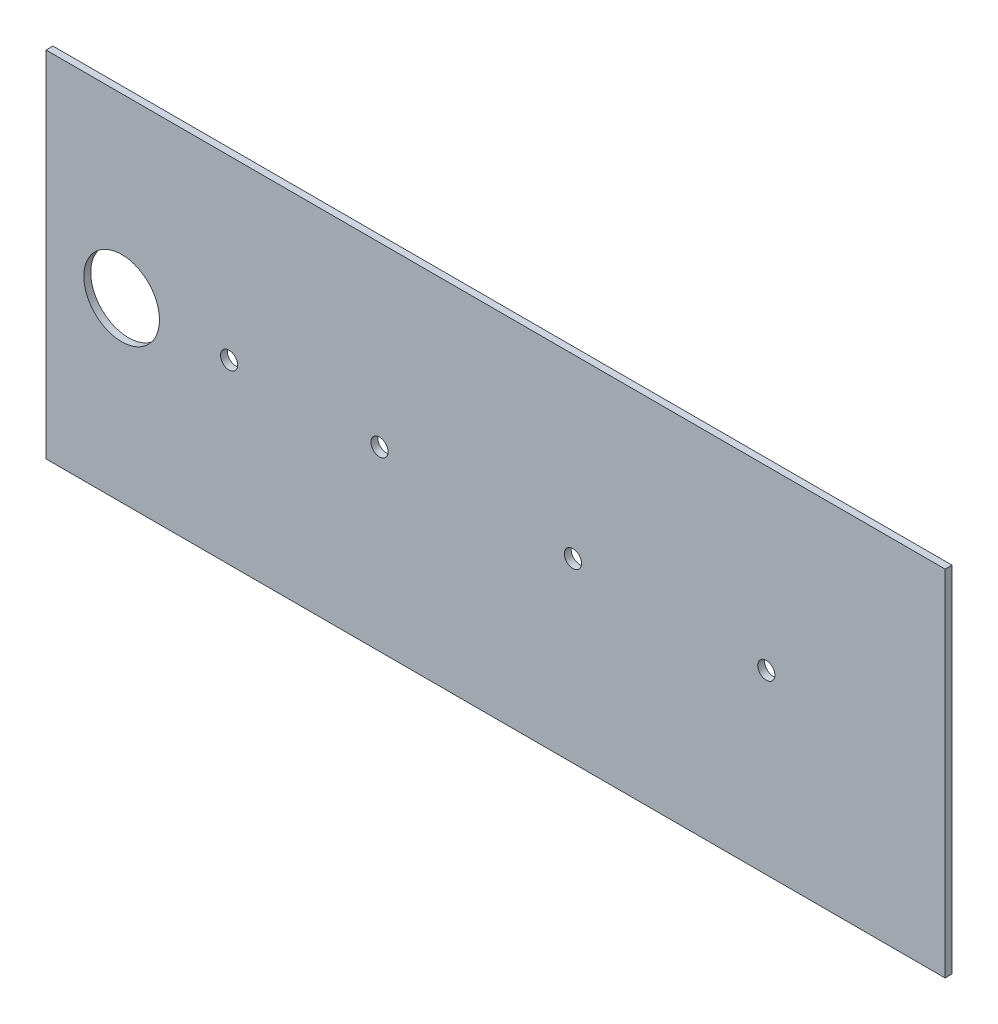
SolidWorks part; units mm, degrees
material "Сталь ШХ15 ГОСТ 801-78"
ref_plane "Plane1" through (0, 0, 0) normal (0, 0, 1) x (1, 0, 0)
ref_plane "Plane2" through (0, 0, 0) normal (0, 1, 0) x (1, 0, 0)
ref_plane "Plane3" through (0, 0, 0) normal (1, 0, 0) x (0, 0, -1)
sketch "Эскиз1" plane through (0, 0, 0) normal (0, 0, 1) x (1, 0, 0)
  line L0 (0, 51.5) -> (261.5, 51.5) construction
  line L1 (0, 0) -> (261.5, 0)
  line L2 (0, 0) -> (0, 103)
  line L3 (0, 103) -> (261.5, 103)
  line L4 (261.5, 0) -> (261.5, 103)
  circle A0 centre (22, 51.5) radius 11
  circle A1 centre (53.25, 51.5) radius 2.5
  circle A2 centre (97, 51.5) radius 2.5
  circle A3 centre (153.25, 51.5) radius 2.5
  circle A4 centre (209.5, 51.5) radius 2.5
  dimension "D3" = 22
  dimension "D4" = 22
  dimension "D5" = 5
  dimension "D6" = 31.25
  dimension "D9" = 52
  dimension "D1" = 103
  dimension "D2" = 56.25
  dimension "D7" = 43.75
  dimension "D8" = 56.25
extrude "Бобышка-Вытянуть1" add sketch "Эскиз1" along normal blind 2 contours L2 L0 A0 A1 A2 A3 A4 L4 L3 | L0 L2 L1 L4 A4 A3 A2 A1 A0 region at (132.3188, 77.6259, 0) region at (132.3188, 25.3741, 0)
